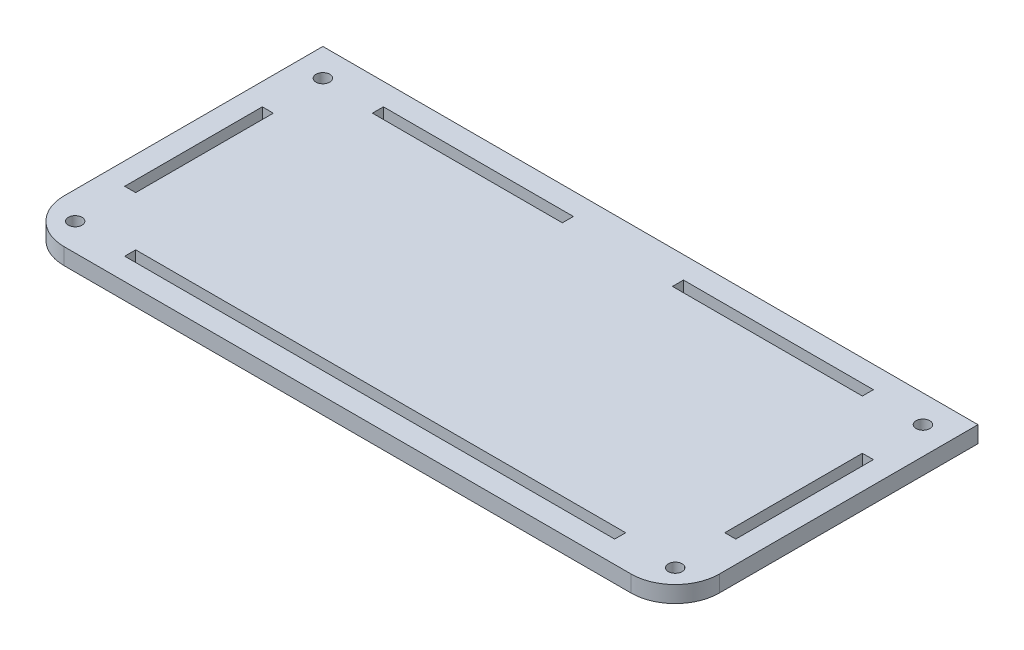
SolidWorks part; units mm, degrees
material "PVC rigido"
ref_plane "Piano frontale" through (0, 0, 0) normal (0, 0, 1) x (1, 0, 0)
ref_plane "Piano superiore" through (0, 0, 0) normal (0, 1, 0) x (1, 0, 0)
ref_plane "Piano destro" through (0, 0, 0) normal (1, 0, 0) x (0, 0, -1)
sketch "Schizzo1" plane through (0, 0, 0) normal (0, 1, 0) x (1, 0, 0)
  line L1 (-59.5, -27.5) -> (59.5, -27.5)
  line L2 (-59.5, -27.5) -> (-59.5, 27.5)
  line L3 (-59.5, 27.5) -> (59.5, 27.5)
  line L4 (59.5, -27.5) -> (59.5, 27.5)
  line L5 (-59.5, -27.5) -> (59.5, 27.5) construction
  line L6 (-59.5, 27.5) -> (59.5, -27.5) construction
  line L7 (67.5, 0) -> (59.5, 0) construction
  line L8 (67.5, -27.5) -> (67.5, 26.5) construction
  line L9 (-59.5, 0) -> (-67.5, 0) construction
  line L10 (-67.5, 26.5) -> (-67.5, -27.5) construction
  point P0 (0, 0)
  dimension "D1" = 8
  dimension "D2" = 55
extrude "Estrusione-Estrusione1" add sketch "Schizzo1" along normal blind 3
hole_wizard "Foro filettato M3x0.5-1" positions "Schizzo3" profile "Schizzo2" tap size "M3x0.5" standard "Ansi Metric" end condition through all
sketch "Schizzo3" plane through (0, 3, 0) normal (0, 1, 0) x (1, 0, 0)
  line L16 (54.5, -22.5) -> (54.5, 22.5)
  line L17 (54.5, 22.5) -> (-54.5, 22.5)
  line L18 (-54.5, 22.5) -> (-54.5, -22.5)
  line L19 (-54.5, -22.5) -> (54.5, -22.5)
  line L20 (54.5, -22.5) -> (54.5, 22.5) construction
  line L21 (54.5, 22.5) -> (-54.5, 22.5) construction
  line L22 (-54.5, 22.5) -> (-54.5, -22.5) construction
  line L23 (-54.5, -22.5) -> (54.5, -22.5) construction
  point P0 (-54.5, -22.5)
  point P2 (54.5, -22.5)
  point P4 (54.5, 22.5)
  point P6 (-54.5, 22.5)
  dimension "D1" = 5
sketch "Schizzo2" plane through (-54.5, 3, 22.5) normal (1, 0, 0) x (0, 0, 1)
  line L0 (0, 0) -> (0, 3)
  line L1 (0, 3) -> (1.25, 3)
  line L2 (1.25, 3) -> (1.25, 0)
  line L5 (1.25, 0) -> (0, 0)
  line L11 (0, -6.35) -> (0, 107.95) construction
  dimension "Thru Tap Drill Dia." = 2.5
  dimension "Thru Tap Drill Depth" = 3
cosmetic thread "Filettatura del foro1" parameters "D2"=3
cosmetic thread "Filettatura del foro2" parameters "D2"=3
cosmetic thread "Filettatura del foro3" parameters "D2"=3
cosmetic thread "Filettatura del foro4" parameters "D2"=3
sketch "Schizzo4" plane through (0, 3, 0) normal (0, 1, 0) x (1, 0, 0)
  line L0 (-54.5, -22.5) -> (-44.5, -22.5) construction
  line L1 (-44.5, -22.5) -> (44.5, -22.5) construction
  line L2 (44.5, -22.5) -> (54.5, -22.5) construction
  line L3 (54.5, -22.5) -> (54.5, -12.5) construction
  line L4 (54.5, -12.5) -> (54.5, 12.5) construction
  line L5 (54.5, 12.5) -> (54.5, 22.5) construction
  line L6 (-54.5, -22.5) -> (-54.5, -12.5) construction
  line L7 (-54.5, -12.5) -> (-54.5, 12.5) construction
  line L8 (-54.5, 12.5) -> (-54.5, 22.5) construction
  line L10 (-44.5, -23.5) -> (44.5, -23.5)
  line L11 (-44.5, -23.5) -> (-44.5, -21.5)
  line L12 (-44.5, -21.5) -> (44.5, -21.5)
  line L13 (44.5, -23.5) -> (44.5, -21.5)
  line L14 (53.5, 12.5) -> (55.5, 12.5)
  line L15 (53.5, 12.5) -> (53.5, -12.5)
  line L16 (53.5, -12.5) -> (55.5, -12.5)
  line L17 (55.5, 12.5) -> (55.5, -12.5)
  line L18 (-53.5, -12.5) -> (-55.5, -12.5)
  line L19 (-53.5, -12.5) -> (-53.5, 12.5)
  line L20 (-53.5, 12.5) -> (-55.5, 12.5)
  line L21 (-55.5, -12.5) -> (-55.5, 12.5)
  dimension "D1" = 10
  dimension "D2" = 2
extrude "Taglio-Estrusione1" cut sketch "Schizzo4" against normal through all
fillet "Raccordo1" radius 8 2 edges at (-59.5, 1.5, 27.5) (59.5, 1.5, 27.5)
sketch "Schizzo5" plane through (0, 3, 0) normal (0, 1, 0) x (1, 0, 0)
  line L0 (44.5, -23.5) -> (44.5, -21.5) construction
  line L1 (44.5, 23.5) -> (10, 23.5)
  line L2 (44.5, 23.5) -> (44.5, 21.5)
  line L3 (44.5, 21.5) -> (10, 21.5)
  line L4 (-44.5, 23.5) -> (-44.5, 21.5)
  line L6 (0, -21.5) -> (0, 0) construction
  line L7 (44.5, -21.5) -> (-44.5, -21.5) construction
  line L8 (0, 0) -> (0, 21.5) construction
  line L9 (10, 21.5) -> (10, 23.5)
  line L10 (-10, 21.5) -> (-10, 23.5)
  line L11 (-10, 23.5) -> (-44.5, 23.5)
  line L12 (-10, 21.5) -> (-44.5, 21.5)
  line L13 (10, 21.5) -> (-10, 21.5) construction
  dimension "D1" = 20
extrude "Taglio-Estrusione2" cut sketch "Schizzo5" against normal blind 10
